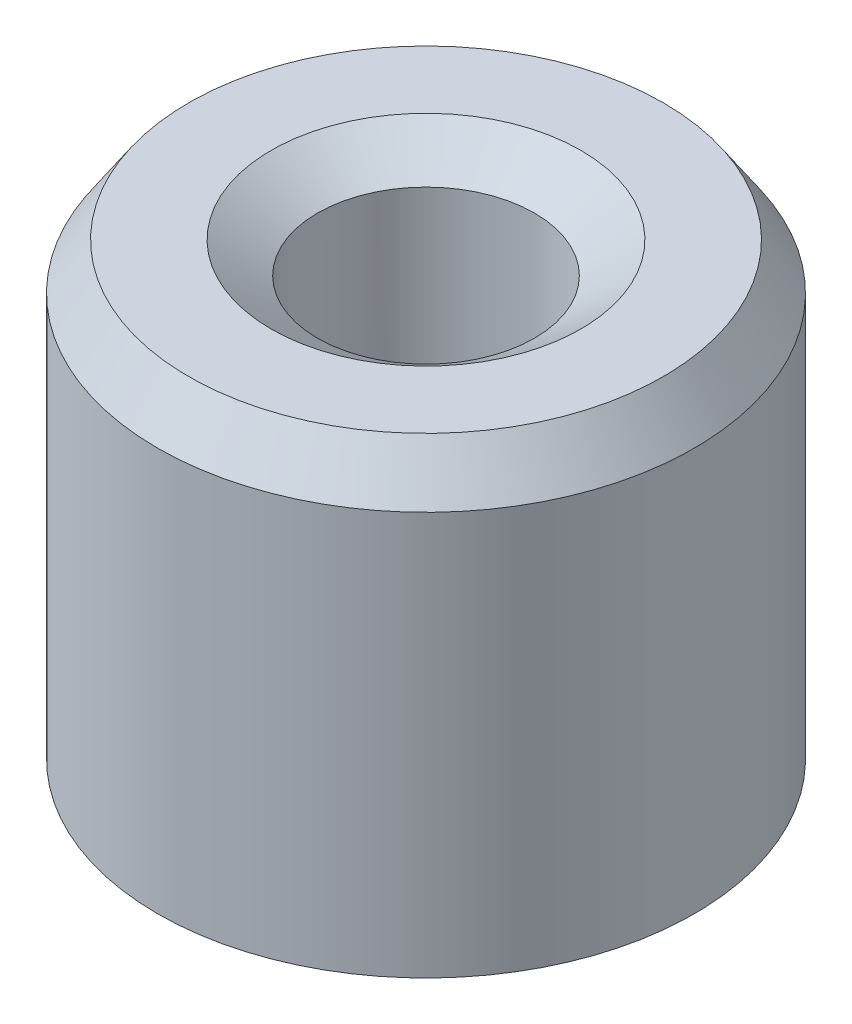
SolidWorks part; units mm, degrees
ref_plane "Front Plane" through (0, 0, 0) normal (0, 0, 1) x (1, 0, 0)
ref_plane "Top Plane" through (0, 0, 0) normal (0, 1, 0) x (1, 0, 0)
ref_plane "Right Plane" through (0, 0, 0) normal (1, 0, 0) x (0, 0, -1)
sketch "Sketch1" plane through (0, 0, 0) normal (0, 1, 0) x (1, 0, 0)
  circle A0 centre (0, 0) radius 5
  dimension "SLEEVE_OD" = 10
extrude "Boss-Extrude1" add sketch "Sketch1" along normal blind 8.9579
sketch "Sketch2" plane through (0, 0, 0) normal (0, 1, 0) x (1, 0, 0)
  circle A0 centre (0, 0) radius 2.0206
  dimension "BORE_D" = 4.0412
extrude "Cut-Extrude1" cut sketch "Sketch2" along normal through all
chamfer "Chamfer1" distance 0.8638 angle 33.883 4 edges at (0, 8.9579, 2.0206) (0, 0, 2.0206) (0, 0, 5) (0, 8.9579, 5) first distance on face at (0, 8.9579, 2.0206) first distance on face at (0, 0, 2.0206) first distance on face at (0, 8.9579, 5)
